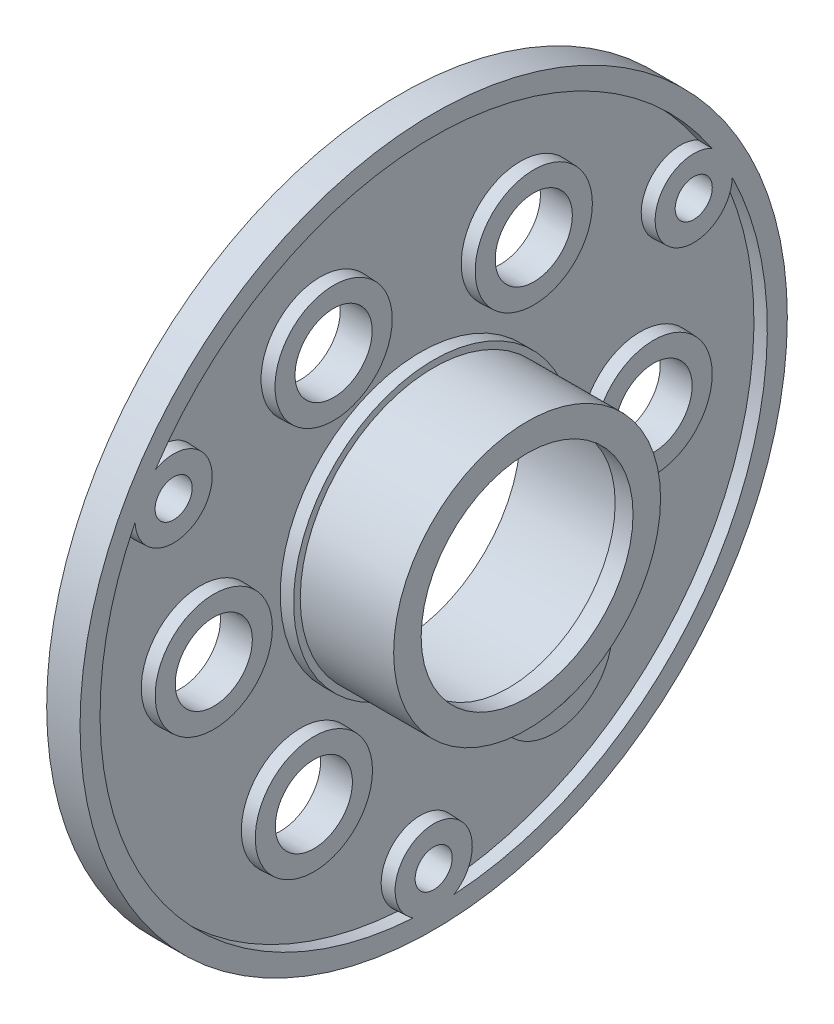
SolidWorks part; units mm, degrees
material "ABS"
ref_plane "Front Plane" through (0, 0, 0) normal (0, 0, 1) x (1, 0, 0)
ref_plane "Top Plane" through (0, 0, 0) normal (0, 1, 0) x (1, 0, 0)
ref_plane "Right Plane" through (0, 0, 0) normal (1, 0, 0) x (0, 0, -1)
ref_axis "Axis1" through (-88.99, 0, 0) along (1, 0, 0)
sketch "Sketch4" plane through (0, 0, 0) normal (1, 0, 0) x (0, 0, -1)
  circle A0 centre (0, 0) radius 26.5
  dimension "D1" = 53
extrude "Boss-Extrude1" add sketch "Sketch4" along normal mid plane 2.5
sketch "Sketch3" plane through (-1.25, 0, 0) normal (1, 0, 0) x (0, 0, -1)
  line L0 (0, 0) -> (0, 14.6969) construction
  line L1 (0, 0) -> (19.4856, 11.25) construction
  circle A0 centre (7.5, 14.6969) radius 3
  circle A2 centre (7.5, 14.6969) radius 7.5 construction
  circle A4 centre (-7.5, 14.6969) radius 3
  circle A6 centre (-7.5, 14.6969) radius 7.5 construction
  circle A7 centre (0, 0) radius 9 construction
  circle A10 centre (19.4856, 11.25) radius 1.5
  circle A11 centre (16.4779, -0.8533) radius 3
  circle A14 centre (8.9779, -13.8437) radius 3
  circle A15 centre (0, -22.5) radius 1.5
  circle A18 centre (-8.9779, -13.8437) radius 3
  circle A19 centre (-16.4779, -0.8533) radius 3
  circle A22 centre (-19.4856, 11.25) radius 1.5
  point P26 (0, 0)
  dimension "D1" = 6
  dimension "D2" = 6
  dimension "D3" = 15
  dimension "D4" = 15
  dimension "D5" = 18
  dimension "D6" = 3
  dimension "D9" = 3
  dimension "D7" = 60
  dimension "D8" = 22.5
extrude "Cut-Extrude2" cut sketch "Sketch3" along normal through all draft 2.5
sketch "Sketch5" plane through (1.25, 0, 0) normal (1, 0, 0) x (0, 0, -1)
  circle A0 centre (0, 0) radius 10
  dimension "D1" = 20
extrude "Boss-Extrude2" add sketch "Sketch5" along normal blind 7
sketch "Sketch6" plane through (1.25, 0, 0) normal (1, 0, 0) x (0, 0, -1)
  circle A0 centre (0, 0) radius 9
  dimension "D1" = 18
extrude "Cut-Extrude3" cut sketch "Sketch6" against normal through all and the other way blind 5.6
sketch "Sketch8" plane through (6.85, 0, 0) normal (-1, 0, 0) x (0, 0, 1)
  circle A0 centre (0, 0) radius 8
  dimension "D1" = 16
extrude "Cut-Extrude5" cut sketch "Sketch8" against normal blind 10 draft 2.5
shell "Shell2" thickness 1.5 removed face at (1.25, 0, -10)
